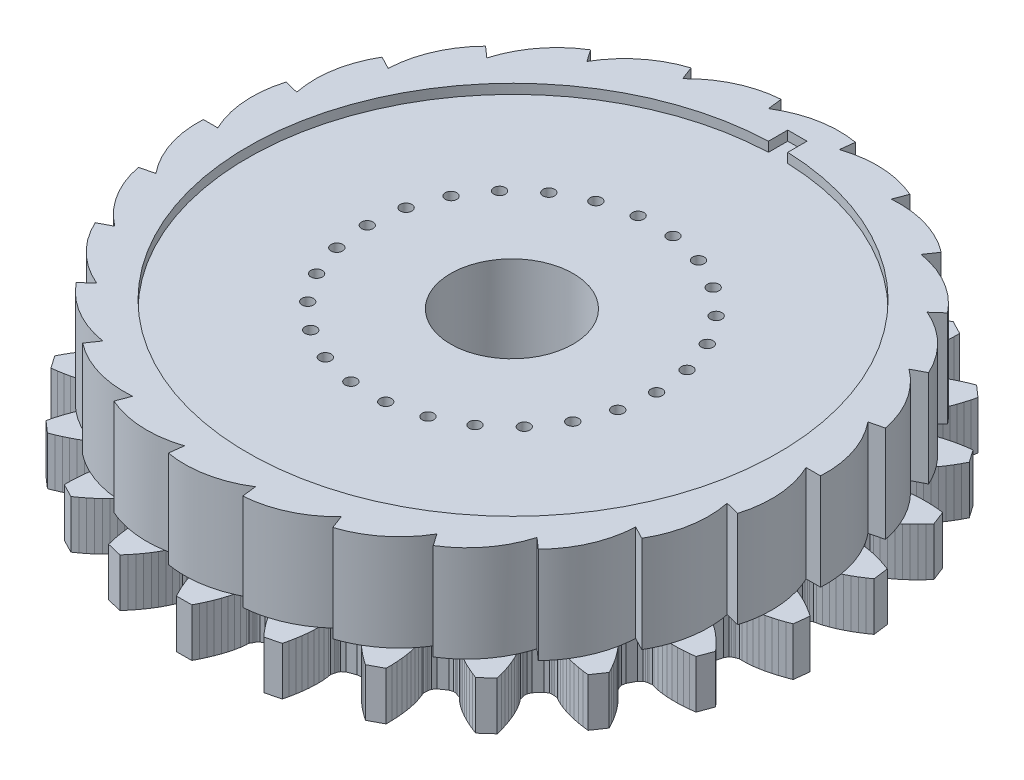
SolidWorks part; units mm, degrees
material "1060 Alloy"
ref_plane "Front Plane" through (0, 0, 0) normal (0, 0, 1) x (1, 0, 0)
ref_plane "Top Plane" through (0, 0, 0) normal (0, 1, 0) x (1, 0, 0)
ref_plane "Right Plane" through (0, 0, 0) normal (1, 0, 0) x (0, 0, -1)
sketch "Sketch1" plane through (0, 0, 0) normal (0, 1, 0) x (1, 0, 0)
  line L0 (0, 0) -> (54.8903, 0) construction
  line L1 (0, 0) -> (47.5263, 11.7142) construction
  line L2 (0, 0) -> (29.6137, 7.2991)
  line L3 (0, 0) -> (32, 0)
  circle A0 centre (0, 0) radius 32 construction
  circle A1 centre (0, 0) radius 30.5 construction
  arc A2 (29.6137, 7.2991) -> (32, 0) centre (21.3514, 0.5583) cw
  circle A3 centre (0, 0) radius 31.25 construction
  dimension "D1" = 62.5
  dimension "D2" = 1.5
  dimension "D4" = 0.75
  dimension "D3" = 13.846
extrude "Extrude ratchet edge" add sketch "Sketch1" along normal blind 10
pattern_circular "Pattern edge to form gear" count 26 over 360 about axis through (0, 10, 0) along (0, -1, 0) of "Extrude ratchet edge" reverse direction yes
sketch "Sketch7" plane through (0, 10, 0) normal (0, 1, 0) x (1, 0, 0)
  circle A0 centre (0, 0) radius 6.35
  dimension "D1" = 12.7
sketch "Sketch12" plane through (0, 0, 0) normal (0, -1, 0) x (1, 0, 0)
  line L0 (29.0003, -0.6166) -> (29.1196, -1.0003)
  line L1 (29.1196, -1.0003) -> (29.244, -1.1506)
  line L2 (29.244, -1.1506) -> (29.3694, -1.2597)
  line L3 (29.3694, -1.2597) -> (29.4955, -1.346)
  line L4 (29.4955, -1.346) -> (29.7463, -1.5351)
  line L5 (29.7463, -1.5351) -> (30.0039, -1.5796)
  line L6 (30.0039, -1.5796) -> (30.5166, -1.7122)
  line L7 (30.5166, -1.7122) -> (31.0266, -1.8861)
  line L8 (31.0266, -1.8861) -> (31.5336, -2.0936)
  line L9 (31.5336, -2.0936) -> (32.0376, -2.3308)
  line L10 (32.0376, -2.3308) -> (32.5381, -2.595)
  line L11 (32.5381, -2.595) -> (33.035, -2.8848)
  line L12 (33.035, -2.8848) -> (33.5277, -3.1987)
  line L13 (33.5277, -3.1987) -> (34.0159, -3.5359)
  line L14 (34.0159, -3.5359) -> (33.8164, -5.1042)
  line L15 (33.8164, -5.1042) -> (33.2594, -5.3084)
  line L16 (33.2594, -5.3084) -> (32.7038, -5.4891)
  line L17 (32.7038, -5.4891) -> (32.1503, -5.6453)
  line L18 (32.1503, -5.6453) -> (31.5995, -5.7759)
  line L19 (31.5995, -5.7759) -> (31.0523, -5.8793)
  line L20 (31.0523, -5.8793) -> (30.5094, -5.9534)
  line L21 (30.5094, -5.9534) -> (29.9722, -5.9942)
  line L22 (29.9722, -5.9942) -> (29.4426, -5.9942)
  line L23 (29.4426, -5.9942) -> (29.182, -5.9728)
  line L24 (29.182, -5.9728) -> (28.8919, -6.0931)
  line L25 (28.8919, -6.0931) -> (28.7482, -6.1452)
  line L26 (28.7482, -6.1452) -> (28.5995, -6.2194)
  line L27 (28.5995, -6.2194) -> (28.4414, -6.3338)
  line L28 (28.4414, -6.3338) -> (28.2299, -6.6755)
  line L29 (28.2299, -6.6755) -> (28.0119, -7.539)
  line L30 (28.0119, -7.539) -> (28.0359, -7.9401)
  line L31 (28.0359, -7.9401) -> (28.1207, -8.1159)
  line L32 (28.1207, -8.1159) -> (28.2164, -8.2517)
  line L33 (28.2164, -8.2517) -> (28.3182, -8.3658)
  line L34 (28.3182, -8.3658) -> (28.5164, -8.6094)
  line L35 (28.5164, -8.6094) -> (28.7559, -8.7142)
  line L36 (28.7559, -8.7142) -> (29.222, -8.9657)
  line L37 (29.222, -8.9657) -> (29.6755, -9.2566)
  line L38 (29.6755, -9.2566) -> (30.1181, -9.5794)
  line L39 (30.1181, -9.5794) -> (30.5507, -9.9303)
  line L40 (30.5507, -9.9303) -> (30.9735, -10.3067)
  line L41 (30.9735, -10.3067) -> (31.3865, -10.7069)
  line L42 (31.3865, -10.7069) -> (31.7898, -11.1296)
  line L43 (31.7898, -11.1296) -> (32.1831, -11.5738)
  line L44 (32.1831, -11.5738) -> (31.6141, -13.0488)
  line L45 (31.6141, -13.0488) -> (31.0244, -13.1138)
  line L46 (31.0244, -13.1138) -> (30.4418, -13.1563)
  line L47 (30.4418, -13.1563) -> (29.8669, -13.1754)
  line L48 (29.8669, -13.1754) -> (29.3009, -13.1704)
  line L49 (29.3009, -13.1704) -> (28.7448, -13.1399)
  line L50 (28.7448, -13.1399) -> (28.2, -13.0819)
  line L51 (28.2, -13.0819) -> (27.6686, -12.9929)
  line L52 (27.6686, -12.9929) -> (27.1544, -12.8663)
  line L53 (27.1544, -12.8663) -> (26.9065, -12.7831)
  line L54 (26.9065, -12.7831) -> (26.5961, -12.8305)
  line L55 (26.5961, -12.8305) -> (26.4441, -12.8467)
  line L56 (26.4441, -12.8467) -> (26.2819, -12.8831)
  line L57 (26.2819, -12.8831) -> (26.1011, -12.9564)
  line L58 (26.1011, -12.9564) -> (25.814, -13.2375)
  line L59 (25.814, -13.2375) -> (25.3956, -14.0238)
  line L60 (25.3956, -14.0238) -> (25.3229, -14.4189)
  line L61 (25.3229, -14.4189) -> (25.3632, -14.6099)
  line L62 (25.3632, -14.6099) -> (25.4236, -14.7647)
  line L63 (25.4236, -14.7647) -> (25.4951, -14.8998)
  line L64 (25.4951, -14.8998) -> (25.6292, -15.1838)
  line L65 (25.6292, -15.1838) -> (25.8367, -15.3428)
  line L66 (25.8367, -15.3428) -> (26.2291, -15.6985)
  line L67 (26.2291, -15.6985) -> (26.5998, -16.0895)
  line L68 (26.5998, -16.0895) -> (26.9523, -16.5089)
  line L69 (26.9523, -16.5089) -> (27.2883, -16.9531)
  line L70 (27.2883, -16.9531) -> (27.6087, -17.4197)
  line L71 (27.6087, -17.4197) -> (27.914, -17.9072)
  line L72 (27.914, -17.9072) -> (28.2044, -18.4141)
  line L73 (28.2044, -18.4141) -> (28.48, -18.9395)
  line L74 (28.48, -18.9395) -> (27.5746, -20.2355)
  line L75 (27.5746, -20.2355) -> (26.9864, -20.1575)
  line L76 (26.9864, -20.1575) -> (26.4105, -20.0593)
  line L77 (26.4105, -20.0593) -> (25.8478, -19.9403)
  line L78 (25.8478, -19.9403) -> (25.2994, -19.8)
  line L79 (25.2994, -19.8) -> (24.7668, -19.6373)
  line L80 (24.7668, -19.6373) -> (24.2517, -19.4506)
  line L81 (24.2517, -19.4506) -> (23.7571, -19.237)
  line L82 (23.7571, -19.237) -> (23.2881, -18.991)
  line L83 (23.2881, -18.991) -> (23.0673, -18.8509)
  line L84 (23.0673, -18.8509) -> (22.7546, -18.8226)
  line L85 (22.7546, -18.8226) -> (22.6031, -18.802)
  line L86 (22.6031, -18.802) -> (22.4369, -18.7985)
  line L87 (22.4369, -18.7985) -> (22.2438, -18.8264)
  line L88 (22.2438, -18.8264) -> (21.8978, -19.0306)
  line L89 (21.8978, -19.0306) -> (21.3034, -19.694)
  line L90 (21.3034, -19.694) -> (21.1383, -20.0602)
  line L91 (21.1383, -20.0602) -> (21.1316, -20.2553)
  line L92 (21.1316, -20.2553) -> (21.1532, -20.4201)
  line L93 (21.1532, -20.4201) -> (21.1903, -20.5684)
  line L94 (21.1903, -20.5684) -> (21.2526, -20.8761)
  line L95 (21.2526, -20.8761) -> (21.416, -21.0803)
  line L96 (21.416, -21.0803) -> (21.7119, -21.5195)
  line L97 (21.7119, -21.5195) -> (21.9782, -21.9879)
  line L98 (21.9782, -21.9879) -> (22.2201, -22.4794)
  line L99 (22.2201, -22.4794) -> (22.4401, -22.9911)
  line L100 (22.4401, -22.9911) -> (22.6395, -23.5209)
  line L101 (22.6395, -23.5209) -> (22.8193, -24.0672)
  line L102 (22.8193, -24.0672) -> (22.9799, -24.6289)
  line L103 (22.9799, -24.6289) -> (23.1217, -25.205)
  line L104 (23.1217, -25.205) -> (21.9325, -26.2467)
  line L105 (21.9325, -26.2467) -> (21.3801, -26.0302)
  line L106 (21.3801, -26.0302) -> (20.8445, -25.797)
  line L107 (20.8445, -25.797) -> (20.3266, -25.5468)
  line L108 (20.3266, -25.5468) -> (19.8277, -25.2793)
  line L109 (19.8277, -25.2793) -> (19.3494, -24.9939)
  line L110 (19.3494, -24.9939) -> (18.894, -24.6893)
  line L111 (18.894, -24.6893) -> (18.4649, -24.3636)
  line L112 (18.4649, -24.3636) -> (18.0684, -24.0125)
  line L113 (18.0684, -24.0125) -> (17.8876, -23.8237)
  line L114 (17.8876, -23.8237) -> (17.5907, -23.7213)
  line L115 (17.5907, -23.7213) -> (17.4485, -23.665)
  line L116 (17.4485, -23.665) -> (17.288, -23.6219)
  line L117 (17.288, -23.6219) -> (17.0938, -23.6028)
  line L118 (17.0938, -23.6028) -> (16.709, -23.7182)
  line L119 (16.709, -23.7182) -> (15.9732, -24.22)
  line L120 (15.9732, -24.22) -> (15.7251, -24.5362)
  line L121 (15.7251, -24.5362) -> (15.672, -24.7239)
  line L122 (15.672, -24.7239) -> (15.6536, -24.8891)
  line L123 (15.6536, -24.8891) -> (15.6541, -25.042)
  line L124 (15.6541, -25.042) -> (15.641, -25.3558)
  line L125 (15.641, -25.3558) -> (15.7507, -25.593)
  line L126 (15.7507, -25.593) -> (15.9329, -26.0903)
  line L127 (15.9329, -26.0903) -> (16.0794, -26.6088)
  line L128 (16.0794, -26.6088) -> (16.1966, -27.144)
  line L129 (16.1966, -27.144) -> (16.2878, -27.6934)
  line L130 (16.2878, -27.6934) -> (16.3546, -28.2555)
  line L131 (16.3546, -28.2555) -> (16.3984, -28.829)
  line L132 (16.3984, -28.829) -> (16.4199, -29.4128)
  line L133 (16.4199, -29.4128) -> (16.4198, -30.0061)
  line L134 (16.4198, -30.0061) -> (15.0158, -30.7329)
  line L135 (15.0158, -30.7329) -> (14.5313, -30.3905)
  line L136 (14.5313, -30.3905) -> (14.067, -30.0359)
  line L137 (14.067, -30.0359) -> (13.624, -29.6691)
  line L138 (13.624, -29.6691) -> (13.2037, -29.29)
  line L139 (13.2037, -29.29) -> (12.8076, -28.8984)
  line L140 (12.8076, -28.8984) -> (12.4383, -28.4937)
  line L141 (12.4383, -28.4937) -> (12.0996, -28.0747)
  line L142 (12.0996, -28.0747) -> (11.7986, -27.6389)
  line L143 (11.7986, -27.6389) -> (11.6683, -27.4123)
  line L144 (11.6683, -27.4123) -> (11.4045, -27.2419)
  line L145 (11.4045, -27.2419) -> (11.28, -27.1532)
  line L146 (11.28, -27.1532) -> (11.1345, -27.0729)
  line L147 (11.1345, -27.0729) -> (10.9505, -27.0079)
  line L148 (10.9505, -27.0079) -> (10.5492, -27.0279)
  line L149 (10.5492, -27.0279) -> (9.7146, -27.339)
  line L150 (9.7146, -27.339) -> (9.3982, -27.5866)
  line L151 (9.3982, -27.5866) -> (9.3017, -27.7562)
  line L152 (9.3017, -27.7562) -> (9.2442, -27.9122)
  line L153 (9.2442, -27.9122) -> (9.2082, -28.0607)
  line L154 (9.2082, -28.0607) -> (9.1203, -28.3622)
  line L155 (9.1203, -28.3622) -> (9.1701, -28.6189)
  line L156 (9.1701, -28.6189) -> (9.2279, -29.1453)
  line L157 (9.2279, -29.1453) -> (9.2461, -29.6838)
  line L158 (9.2461, -29.6838) -> (9.2319, -30.2315)
  line L159 (9.2319, -30.2315) -> (9.1888, -30.7868)
  line L160 (9.1888, -30.7868) -> (9.1192, -31.3485)
  line L161 (9.1192, -31.3485) -> (9.0245, -31.9158)
  line L162 (9.0245, -31.9158) -> (8.9057, -32.4878)
  line L163 (8.9057, -32.4878) -> (8.7636, -33.0638)
  line L164 (8.7636, -33.0638) -> (7.2264, -33.4335)
  line L165 (7.2264, -33.4335) -> (6.8379, -32.9851)
  line L166 (6.8379, -32.9851) -> (6.472, -32.5297)
  line L167 (6.472, -32.5297) -> (6.1297, -32.0675)
  line L168 (6.1297, -32.0675) -> (5.8123, -31.5988)
  line L169 (5.8123, -31.5988) -> (5.5215, -31.1238)
  line L170 (5.5215, -31.1238) -> (5.2598, -30.6425)
  line L171 (5.2598, -30.6425) -> (5.0311, -30.1547)
  line L172 (5.0311, -30.1547) -> (4.8432, -29.6595)
  line L173 (4.8432, -29.6595) -> (4.7709, -29.4083)
  line L174 (4.7709, -29.4083) -> (4.5555, -29.1797)
  line L175 (4.5555, -29.1797) -> (4.4559, -29.0638)
  line L176 (4.4559, -29.0638) -> (4.3338, -28.951)
  line L177 (4.3338, -28.951) -> (4.1707, -28.8438)
  line L178 (4.1707, -28.8438) -> (3.7763, -28.7672)
  line L179 (3.7763, -28.7672) -> (2.8915, -28.8696)
  line L180 (2.8915, -28.8696) -> (2.525, -29.0342)
  line L181 (2.525, -29.0342) -> (2.3907, -29.1758)
  line L182 (2.3907, -29.1758) -> (2.2976, -29.3135)
  line L183 (2.2976, -29.3135) -> (2.2271, -29.4491)
  line L184 (2.2271, -29.4491) -> (2.0696, -29.7208)
  line L185 (2.0696, -29.7208) -> (2.0565, -29.9819)
  line L186 (2.0565, -29.9819) -> (1.9867, -30.5069)
  line L187 (1.9867, -30.5069) -> (1.8755, -31.0341)
  line L188 (1.8755, -31.0341) -> (1.7306, -31.5624)
  line L189 (1.7306, -31.5624) -> (1.5559, -32.0913)
  line L190 (1.5559, -32.0913) -> (1.3539, -32.6201)
  line L191 (1.3539, -32.6201) -> (1.1262, -33.1482)
  line L192 (1.1262, -33.1482) -> (0.8739, -33.6752)
  line L193 (0.8739, -33.6752) -> (0.5981, -34.2004)
  line L194 (0.5981, -34.2004) -> (-0.9829, -34.1915)
  line L195 (-0.9829, -34.1915) -> (-1.2528, -33.6632)
  line L196 (-1.2528, -33.6632) -> (-1.499, -33.1334)
  line L197 (-1.499, -33.1334) -> (-1.7208, -32.6027)
  line L198 (-1.7208, -32.6027) -> (-1.9169, -32.0717)
  line L199 (-1.9169, -32.0717) -> (-2.0855, -31.5409)
  line L200 (-2.0855, -31.5409) -> (-2.2244, -31.011)
  line L201 (-2.2244, -31.011) -> (-2.3297, -30.4826)
  line L202 (-2.3297, -30.4826) -> (-2.3936, -29.9568)
  line L203 (-2.3936, -29.9568) -> (-2.4037, -29.6956)
  line L204 (-2.4037, -29.6956) -> (-2.5581, -29.4221)
  line L205 (-2.5581, -29.4221) -> (-2.6272, -29.2857)
  line L206 (-2.6272, -29.2857) -> (-2.7187, -29.147)
  line L207 (-2.7187, -29.147) -> (-2.8514, -29.0039)
  line L208 (-2.8514, -29.0039) -> (-3.216, -28.8351)
  line L209 (-3.216, -28.8351) -> (-4.0996, -28.7228)
  line L210 (-4.0996, -28.7228) -> (-4.4948, -28.7949)
  line L211 (-4.4948, -28.7949) -> (-4.6591, -28.9003)
  line L212 (-4.6591, -28.9003) -> (-4.7824, -29.0117)
  line L213 (-4.7824, -29.0117) -> (-4.8834, -29.1265)
  line L214 (-4.8834, -29.1265) -> (-5.1013, -29.3526)
  line L215 (-5.1013, -29.3526) -> (-5.1765, -29.603)
  line L216 (-5.1765, -29.603) -> (-5.37, -30.096)
  line L217 (-5.37, -30.096) -> (-5.6041, -30.5812)
  line L218 (-5.6041, -30.5812) -> (-5.8712, -31.0596)
  line L219 (-5.8712, -31.0596) -> (-6.1674, -31.5313)
  line L220 (-6.1674, -31.5313) -> (-6.4901, -31.9963)
  line L221 (-6.4901, -31.9963) -> (-6.8376, -32.4546)
  line L222 (-6.8376, -32.4546) -> (-7.2086, -32.9059)
  line L223 (-7.2086, -32.9059) -> (-7.6021, -33.3499)
  line L224 (-7.6021, -33.3499) -> (-9.135, -32.9629)
  line L225 (-9.135, -32.9629) -> (-9.2706, -32.3853)
  line L226 (-9.2706, -32.3853) -> (-9.383, -31.812)
  line L227 (-9.383, -31.812) -> (-9.4713, -31.2437)
  line L228 (-9.4713, -31.2437) -> (-9.5346, -30.6812)
  line L229 (-9.5346, -30.6812) -> (-9.5713, -30.1254)
  line L230 (-9.5713, -30.1254) -> (-9.5793, -29.5776)
  line L231 (-9.5793, -29.5776) -> (-9.5551, -29.0394)
  line L232 (-9.5551, -29.0394) -> (-9.4913, -28.5136)
  line L233 (-9.4913, -28.5136) -> (-9.4387, -28.2576)
  line L234 (-9.4387, -28.2576) -> (-9.5231, -27.9551)
  line L235 (-9.5231, -27.9551) -> (-9.5575, -27.8061)
  line L236 (-9.5575, -27.8061) -> (-9.6132, -27.6496)
  line L237 (-9.6132, -27.6496) -> (-9.7078, -27.4789)
  line L238 (-9.7078, -27.4789) -> (-10.0214, -27.2277)
  line L239 (-10.0214, -27.2277) -> (-10.8524, -26.9072)
  line L240 (-10.8524, -26.9072) -> (-11.2535, -26.8827)
  line L241 (-11.2535, -26.8827) -> (-11.4382, -26.9456)
  line L242 (-11.4382, -26.9456) -> (-11.5846, -27.0243)
  line L243 (-11.5846, -27.0243) -> (-11.7101, -27.1116)
  line L244 (-11.7101, -27.1116) -> (-11.9758, -27.279)
  line L245 (-11.9758, -27.279) -> (-12.1087, -27.5041)
  line L246 (-12.1087, -27.5041) -> (-12.4145, -27.9365)
  line L247 (-12.4145, -27.9365) -> (-12.758, -28.3516)
  line L248 (-12.758, -28.3516) -> (-13.1318, -28.7521)
  line L249 (-13.1318, -28.7521) -> (-13.5322, -29.1392)
  line L250 (-13.5322, -29.1392) -> (-13.9568, -29.5135)
  line L251 (-13.9568, -29.5135) -> (-14.4039, -29.8753)
  line L252 (-14.4039, -29.8753) -> (-14.8722, -30.2247)
  line L253 (-14.8722, -30.2247) -> (-15.3605, -30.5616)
  line L254 (-15.3605, -30.5616) -> (-16.7562, -29.819)
  line L255 (-16.7562, -29.819) -> (-16.7497, -29.2258)
  line L256 (-16.7497, -29.2258) -> (-16.7216, -28.6422)
  line L257 (-16.7216, -28.6422) -> (-16.6713, -28.0693)
  line L258 (-16.6713, -28.0693) -> (-16.5981, -27.508)
  line L259 (-16.5981, -27.508) -> (-16.5008, -26.9596)
  line L260 (-16.5008, -26.9596) -> (-16.3775, -26.4258)
  line L261 (-16.3775, -26.4258) -> (-16.2252, -25.909)
  line L262 (-16.2252, -25.909) -> (-16.0374, -25.4138)
  line L263 (-16.0374, -25.4138) -> (-15.925, -25.1778)
  line L264 (-15.925, -25.1778) -> (-15.9346, -24.8639)
  line L265 (-15.9346, -24.8639) -> (-15.9324, -24.711)
  line L266 (-15.9324, -24.711) -> (-15.949, -24.5456)
  line L267 (-15.949, -24.5456) -> (-15.9999, -24.3573)
  line L268 (-15.9999, -24.3573) -> (-16.2444, -24.0384)
  line L269 (-16.2444, -24.0384) -> (-16.9745, -23.5283)
  line L270 (-16.9745, -23.5283) -> (-17.358, -23.4085)
  line L271 (-17.358, -23.4085) -> (-17.5524, -23.4254)
  line L272 (-17.5524, -23.4254) -> (-17.7134, -23.4668)
  line L273 (-17.7134, -23.4668) -> (-17.8562, -23.5215)
  line L274 (-17.8562, -23.5215) -> (-18.1542, -23.6204)
  line L275 (-18.1542, -23.6204) -> (-18.3371, -23.8072)
  line L276 (-18.3371, -23.8072) -> (-18.7375, -24.1538)
  line L277 (-18.7375, -24.1538) -> (-19.1704, -24.4747)
  line L278 (-19.1704, -24.4747) -> (-19.6292, -24.7741)
  line L279 (-19.6292, -24.7741) -> (-20.1106, -25.0541)
  line L280 (-20.1106, -25.0541) -> (-20.6125, -25.316)
  line L281 (-20.6125, -25.316) -> (-21.1332, -25.5603)
  line L282 (-21.1332, -25.5603) -> (-21.6714, -25.7874)
  line L283 (-21.6714, -25.7874) -> (-22.2262, -25.9977)
  line L284 (-22.2262, -25.9977) -> (-23.4036, -24.9426)
  line L285 (-23.4036, -24.9426) -> (-23.2553, -24.3682)
  line L286 (-23.2553, -24.3682) -> (-23.0883, -23.8083)
  line L287 (-23.0883, -23.8083) -> (-22.9024, -23.2641)
  line L288 (-22.9024, -23.2641) -> (-22.6971, -22.7366)
  line L289 (-22.6971, -22.7366) -> (-22.4713, -22.2274)
  line L290 (-22.4713, -22.2274) -> (-22.2239, -21.7386)
  line L291 (-22.2239, -21.7386) -> (-21.9523, -21.2733)
  line L292 (-21.9523, -21.2733) -> (-21.6515, -20.8374)
  line L293 (-21.6515, -20.8374) -> (-21.4858, -20.6352)
  line L294 (-21.4858, -20.6352) -> (-21.4201, -20.3281)
  line L295 (-21.4201, -20.3281) -> (-21.3813, -20.1802)
  line L296 (-21.3813, -20.1802) -> (-21.3578, -20.0157)
  line L297 (-21.3578, -20.0157) -> (-21.3622, -19.8206)
  line L298 (-21.3622, -19.8206) -> (-21.5232, -19.4525)
  line L299 (-21.5232, -19.4525) -> (-22.1101, -18.7825)
  line L300 (-22.1101, -18.7825) -> (-22.4538, -18.5744)
  line L301 (-22.4538, -18.5744) -> (-22.6466, -18.5443)
  line L302 (-22.6466, -18.5443) -> (-22.8128, -18.5459)
  line L303 (-22.8128, -18.5459) -> (-22.9645, -18.5648)
  line L304 (-22.9645, -18.5648) -> (-23.2775, -18.5896)
  line L305 (-23.2775, -18.5896) -> (-23.4999, -18.7272)
  line L306 (-23.4999, -18.7272) -> (-23.9716, -18.9679)
  line L307 (-23.9716, -18.9679) -> (-24.4686, -19.1758)
  line L308 (-24.4686, -19.1758) -> (-24.9858, -19.3568)
  line L309 (-24.9858, -19.3568) -> (-25.5202, -19.5135)
  line L310 (-25.5202, -19.5135) -> (-26.0702, -19.6476)
  line L311 (-26.0702, -19.6476) -> (-26.6342, -19.7602)
  line L312 (-26.6342, -19.7602) -> (-27.2111, -19.8519)
  line L313 (-27.2111, -19.8519) -> (-27.8001, -19.9233)
  line L314 (-27.8001, -19.9233) -> (-28.6909, -18.6171)
  line L315 (-28.6909, -18.6171) -> (-28.4094, -18.0949)
  line L316 (-28.4094, -18.0949) -> (-28.1133, -17.5912)
  line L317 (-28.1133, -17.5912) -> (-27.8025, -17.1073)
  line L318 (-27.8025, -17.1073) -> (-27.4769, -16.6443)
  line L319 (-27.4769, -16.6443) -> (-27.1359, -16.2039)
  line L320 (-27.1359, -16.2039) -> (-26.7786, -15.7885)
  line L321 (-26.7786, -15.7885) -> (-26.4036, -15.4018)
  line L322 (-26.4036, -15.4018) -> (-26.0072, -15.0505)
  line L323 (-26.0072, -15.0505) -> (-25.7979, -14.8938)
  line L324 (-25.7979, -14.8938) -> (-25.6606, -14.6114)
  line L325 (-25.6606, -14.6114) -> (-25.5876, -14.4771)
  line L326 (-25.5876, -14.4771) -> (-25.5254, -14.3229)
  line L327 (-25.5254, -14.3229) -> (-25.483, -14.1325)
  line L328 (-25.483, -14.1325) -> (-25.5512, -13.7365)
  line L329 (-25.5512, -13.7365) -> (-25.9607, -12.9455)
  line L330 (-25.9607, -12.9455) -> (-26.2446, -12.6612)
  line L331 (-26.2446, -12.6612) -> (-26.4246, -12.5859)
  line L332 (-26.4246, -12.5859) -> (-26.5864, -12.5476)
  line L333 (-26.5864, -12.5476) -> (-26.7382, -12.5297)
  line L334 (-26.7382, -12.5297) -> (-27.0481, -12.4789)
  line L335 (-27.0481, -12.4789) -> (-27.2968, -12.5592)
  line L336 (-27.2968, -12.5592) -> (-27.8125, -12.6801)
  line L337 (-27.8125, -12.6801) -> (-28.3448, -12.763)
  line L338 (-28.3448, -12.763) -> (-28.8902, -12.8149)
  line L339 (-28.8902, -12.8149) -> (-29.4467, -12.8392)
  line L340 (-29.4467, -12.8392) -> (-30.0127, -12.8378)
  line L341 (-30.0127, -12.8378) -> (-30.5873, -12.8121)
  line L342 (-30.5873, -12.8121) -> (-31.1694, -12.7631)
  line L343 (-31.1694, -12.7631) -> (-31.7584, -12.6915)
  line L344 (-31.7584, -12.6915) -> (-32.3107, -11.2101)
  line L345 (-32.3107, -11.2101) -> (-31.9124, -10.7704)
  line L346 (-31.9124, -10.7704) -> (-31.5044, -10.3522)
  line L347 (-31.5044, -10.3522) -> (-31.0868, -9.9567)
  line L348 (-31.0868, -9.9567) -> (-30.6598, -9.5851)
  line L349 (-30.6598, -9.5851) -> (-30.2233, -9.2392)
  line L350 (-30.2233, -9.2392) -> (-29.7771, -8.9214)
  line L351 (-29.7771, -8.9214) -> (-29.3203, -8.6356)
  line L352 (-29.3203, -8.6356) -> (-28.8514, -8.3894)
  line L353 (-28.8514, -8.3894) -> (-28.6108, -8.2873)
  line L354 (-28.6108, -8.2873) -> (-28.4098, -8.0459)
  line L355 (-28.4098, -8.0459) -> (-28.3068, -7.933)
  line L356 (-28.3068, -7.933) -> (-28.2095, -7.7982)
  line L357 (-28.2095, -7.7982) -> (-28.1228, -7.6234)
  line L358 (-28.1228, -7.6234) -> (-28.0943, -7.2226)
  line L359 (-28.0943, -7.2226) -> (-28.3025, -6.3567)
  line L360 (-28.3025, -6.3567) -> (-28.5102, -6.0127)
  line L361 (-28.5102, -6.0127) -> (-28.6669, -5.8964)
  line L362 (-28.6669, -5.8964) -> (-28.8148, -5.8206)
  line L363 (-28.8148, -5.8206) -> (-28.9579, -5.7669)
  line L364 (-28.9579, -5.7669) -> (-29.2466, -5.6433)
  line L365 (-29.2466, -5.6433) -> (-29.5074, -5.6618)
  line L366 (-29.5074, -5.6618) -> (-30.037, -5.6558)
  line L367 (-30.037, -5.6558) -> (-30.5737, -5.6089)
  line L368 (-30.5737, -5.6089) -> (-31.1157, -5.5288)
  line L369 (-31.1157, -5.5288) -> (-31.6618, -5.4192)
  line L370 (-31.6618, -5.4192) -> (-32.211, -5.2824)
  line L371 (-32.211, -5.2824) -> (-32.7628, -5.1199)
  line L372 (-32.7628, -5.1199) -> (-33.3163, -4.933)
  line L373 (-33.3163, -4.933) -> (-33.871, -4.7225)
  line L374 (-33.871, -4.7225) -> (-34.0527, -3.152)
  line L375 (-34.0527, -3.152) -> (-33.5607, -2.8204)
  line L376 (-33.5607, -2.8204) -> (-33.0645, -2.5121)
  line L377 (-33.0645, -2.5121) -> (-32.5644, -2.228)
  line L378 (-32.5644, -2.228) -> (-32.0609, -1.9693)
  line L379 (-32.0609, -1.9693) -> (-31.5543, -1.7379)
  line L380 (-31.5543, -1.7379) -> (-31.045, -1.5361)
  line L381 (-31.045, -1.5361) -> (-30.5331, -1.3679)
  line L382 (-30.5331, -1.3679) -> (-30.0189, -1.2411)
  line L383 (-30.0189, -1.2411) -> (-29.7608, -1.1996)
  line L384 (-29.7608, -1.1996) -> (-29.5079, -1.0133)
  line L385 (-29.5079, -1.0133) -> (-29.3809, -0.9284)
  line L386 (-29.3809, -0.9284) -> (-29.2542, -0.8208)
  line L387 (-29.2542, -0.8208) -> (-29.1281, -0.6718)
  line L388 (-29.1281, -0.6718) -> (-29.0045, -0.2895)
  line L389 (-29.0045, -0.2895) -> (-28.9995, 0.6011)
  line L390 (-28.9995, 0.6011) -> (-29.1188, 0.9848)
  line L391 (-29.1188, 0.9848) -> (-29.2432, 1.1352)
  line L392 (-29.2432, 1.1352) -> (-29.3686, 1.2442)
  line L393 (-29.3686, 1.2442) -> (-29.4947, 1.3306)
  line L394 (-29.4947, 1.3306) -> (-29.7455, 1.5197)
  line L395 (-29.7455, 1.5197) -> (-30.0031, 1.5641)
  line L396 (-30.0031, 1.5641) -> (-30.5158, 1.6968)
  line L397 (-30.5158, 1.6968) -> (-31.0257, 1.8707)
  line L398 (-31.0257, 1.8707) -> (-31.5328, 2.0782)
  line L399 (-31.5328, 2.0782) -> (-32.0368, 2.3153)
  line L400 (-32.0368, 2.3153) -> (-32.5373, 2.5796)
  line L401 (-32.5373, 2.5796) -> (-33.0342, 2.8694)
  line L402 (-33.0342, 2.8694) -> (-33.5269, 3.1833)
  line L403 (-33.5269, 3.1833) -> (-34.0151, 3.5204)
  line L404 (-34.0151, 3.5204) -> (-33.8156, 5.0888)
  line L405 (-33.8156, 5.0888) -> (-33.2586, 5.293)
  line L406 (-33.2586, 5.293) -> (-32.703, 5.4737)
  line L407 (-32.703, 5.4737) -> (-32.1495, 5.6298)
  line L408 (-32.1495, 5.6298) -> (-31.5987, 5.7604)
  line L409 (-31.5987, 5.7604) -> (-31.0515, 5.8639)
  line L410 (-31.0515, 5.8639) -> (-30.5086, 5.9379)
  line L411 (-30.5086, 5.9379) -> (-29.9714, 5.9787)
  line L412 (-29.9714, 5.9787) -> (-29.4418, 5.9788)
  line L413 (-29.4418, 5.9788) -> (-29.1812, 5.9574)
  line L414 (-29.1812, 5.9574) -> (-28.8911, 6.0777)
  line L415 (-28.8911, 6.0777) -> (-28.7474, 6.1298)
  line L416 (-28.7474, 6.1298) -> (-28.5987, 6.2039)
  line L417 (-28.5987, 6.2039) -> (-28.4406, 6.3184)
  line L418 (-28.4406, 6.3184) -> (-28.2291, 6.66)
  line L419 (-28.2291, 6.66) -> (-28.0111, 7.5236)
  line L420 (-28.0111, 7.5236) -> (-28.0351, 7.9247)
  line L421 (-28.0351, 7.9247) -> (-28.1199, 8.1004)
  line L422 (-28.1199, 8.1004) -> (-28.2156, 8.2363)
  line L423 (-28.2156, 8.2363) -> (-28.3174, 8.3504)
  line L424 (-28.3174, 8.3504) -> (-28.5156, 8.594)
  line L425 (-28.5156, 8.594) -> (-28.7551, 8.6988)
  line L426 (-28.7551, 8.6988) -> (-29.2212, 8.9502)
  line L427 (-29.2212, 8.9502) -> (-29.6746, 9.2412)
  line L428 (-29.6746, 9.2412) -> (-30.1173, 9.564)
  line L429 (-30.1173, 9.564) -> (-30.5499, 9.9148)
  line L430 (-30.5499, 9.9148) -> (-30.9727, 10.2912)
  line L431 (-30.9727, 10.2912) -> (-31.3857, 10.6914)
  line L432 (-31.3857, 10.6914) -> (-31.789, 11.1142)
  line L433 (-31.789, 11.1142) -> (-32.1823, 11.5583)
  line L434 (-32.1823, 11.5583) -> (-31.6133, 13.0334)
  line L435 (-31.6133, 13.0334) -> (-31.0236, 13.0984)
  line L436 (-31.0236, 13.0984) -> (-30.4409, 13.1408)
  line L437 (-30.4409, 13.1408) -> (-29.8661, 13.16)
  line L438 (-29.8661, 13.16) -> (-29.3001, 13.155)
  line L439 (-29.3001, 13.155) -> (-28.744, 13.1245)
  line L440 (-28.744, 13.1245) -> (-28.1992, 13.0665)
  line L441 (-28.1992, 13.0665) -> (-27.6678, 12.9775)
  line L442 (-27.6678, 12.9775) -> (-27.1536, 12.8508)
  line L443 (-27.1536, 12.8508) -> (-26.9057, 12.7677)
  line L444 (-26.9057, 12.7677) -> (-26.5953, 12.8151)
  line L445 (-26.5953, 12.8151) -> (-26.4433, 12.8312)
  line L446 (-26.4433, 12.8312) -> (-26.2811, 12.8676)
  line L447 (-26.2811, 12.8676) -> (-26.1002, 12.941)
  line L448 (-26.1002, 12.941) -> (-25.8131, 13.222)
  line L449 (-25.8131, 13.222) -> (-25.3948, 14.0083)
  line L450 (-25.3948, 14.0083) -> (-25.3221, 14.4035)
  line L451 (-25.3221, 14.4035) -> (-25.3623, 14.5945)
  line L452 (-25.3623, 14.5945) -> (-25.4228, 14.7493)
  line L453 (-25.4228, 14.7493) -> (-25.4943, 14.8844)
  line L454 (-25.4943, 14.8844) -> (-25.6284, 15.1683)
  line L455 (-25.6284, 15.1683) -> (-25.8359, 15.3274)
  line L456 (-25.8359, 15.3274) -> (-26.2283, 15.6831)
  line L457 (-26.2283, 15.6831) -> (-26.5989, 16.0741)
  line L458 (-26.5989, 16.0741) -> (-26.9515, 16.4935)
  line L459 (-26.9515, 16.4935) -> (-27.2875, 16.9377)
  line L460 (-27.2875, 16.9377) -> (-27.6079, 17.4043)
  line L461 (-27.6079, 17.4043) -> (-27.9132, 17.8917)
  line L462 (-27.9132, 17.8917) -> (-28.2036, 18.3987)
  line L463 (-28.2036, 18.3987) -> (-28.4792, 18.9241)
  line L464 (-28.4792, 18.9241) -> (-27.5738, 20.2201)
  line L465 (-27.5738, 20.2201) -> (-26.9856, 20.1421)
  line L466 (-26.9856, 20.1421) -> (-26.4097, 20.0438)
  line L467 (-26.4097, 20.0438) -> (-25.847, 19.9249)
  line L468 (-25.847, 19.9249) -> (-25.2986, 19.7846)
  line L469 (-25.2986, 19.7846) -> (-24.766, 19.6219)
  line L470 (-24.766, 19.6219) -> (-24.2509, 19.4351)
  line L471 (-24.2509, 19.4351) -> (-23.7562, 19.2216)
  line L472 (-23.7562, 19.2216) -> (-23.2873, 18.9756)
  line L473 (-23.2873, 18.9756) -> (-23.0665, 18.8355)
  line L474 (-23.0665, 18.8355) -> (-22.7538, 18.8072)
  line L475 (-22.7538, 18.8072) -> (-22.6023, 18.7865)
  line L476 (-22.6023, 18.7865) -> (-22.4361, 18.7831)
  line L477 (-22.4361, 18.7831) -> (-22.243, 18.811)
  line L478 (-22.243, 18.811) -> (-21.897, 19.0152)
  line L479 (-21.897, 19.0152) -> (-21.3026, 19.6785)
  line L480 (-21.3026, 19.6785) -> (-21.1374, 20.0448)
  line L481 (-21.1374, 20.0448) -> (-21.1308, 20.2399)
  line L482 (-21.1308, 20.2399) -> (-21.1524, 20.4046)
  line L483 (-21.1524, 20.4046) -> (-21.1895, 20.5529)
  line L484 (-21.1895, 20.5529) -> (-21.2518, 20.8607)
  line L485 (-21.2518, 20.8607) -> (-21.4152, 21.0648)
  line L486 (-21.4152, 21.0648) -> (-21.7111, 21.5041)
  line L487 (-21.7111, 21.5041) -> (-21.9774, 21.9724)
  line L488 (-21.9774, 21.9724) -> (-22.2193, 22.464)
  line L489 (-22.2193, 22.464) -> (-22.4393, 22.9757)
  line L490 (-22.4393, 22.9757) -> (-22.6387, 23.5054)
  line L491 (-22.6387, 23.5054) -> (-22.8185, 24.0518)
  line L492 (-22.8185, 24.0518) -> (-22.9791, 24.6135)
  line L493 (-22.9791, 24.6135) -> (-23.1209, 25.1896)
  line L494 (-23.1209, 25.1896) -> (-21.9317, 26.2312)
  line L495 (-21.9317, 26.2312) -> (-21.3793, 26.0148)
  line L496 (-21.3793, 26.0148) -> (-20.8436, 25.7815)
  line L497 (-20.8436, 25.7815) -> (-20.3258, 25.5314)
  line L498 (-20.3258, 25.5314) -> (-19.8269, 25.2639)
  line L499 (-19.8269, 25.2639) -> (-19.3486, 24.9785)
  line L500 (-19.3486, 24.9785) -> (-18.8932, 24.6739)
  line L501 (-18.8932, 24.6739) -> (-18.464, 24.3482)
  line L502 (-18.464, 24.3482) -> (-18.0676, 23.997)
  line L503 (-18.0676, 23.997) -> (-17.8868, 23.8082)
  line L504 (-17.8868, 23.8082) -> (-17.5899, 23.7059)
  line L505 (-17.5899, 23.7059) -> (-17.4477, 23.6496)
  line L506 (-17.4477, 23.6496) -> (-17.2872, 23.6065)
  line L507 (-17.2872, 23.6065) -> (-17.093, 23.5873)
  line L508 (-17.093, 23.5873) -> (-16.7082, 23.7028)
  line L509 (-16.7082, 23.7028) -> (-15.9723, 24.2046)
  line L510 (-15.9723, 24.2046) -> (-15.7243, 24.5207)
  line L511 (-15.7243, 24.5207) -> (-15.6712, 24.7085)
  line L512 (-15.6712, 24.7085) -> (-15.6528, 24.8737)
  line L513 (-15.6528, 24.8737) -> (-15.6533, 25.0266)
  line L514 (-15.6533, 25.0266) -> (-15.6401, 25.3403)
  line L515 (-15.6401, 25.3403) -> (-15.7499, 25.5776)
  line L516 (-15.7499, 25.5776) -> (-15.932, 26.0749)
  line L517 (-15.932, 26.0749) -> (-16.0786, 26.5934)
  line L518 (-16.0786, 26.5934) -> (-16.1958, 27.1285)
  line L519 (-16.1958, 27.1285) -> (-16.2869, 27.678)
  line L520 (-16.2869, 27.678) -> (-16.3538, 28.2401)
  line L521 (-16.3538, 28.2401) -> (-16.3976, 28.8136)
  line L522 (-16.3976, 28.8136) -> (-16.4191, 29.3974)
  line L523 (-16.4191, 29.3974) -> (-16.419, 29.9907)
  line L524 (-16.419, 29.9907) -> (-15.015, 30.7175)
  line L525 (-15.015, 30.7175) -> (-14.5305, 30.3751)
  line L526 (-14.5305, 30.3751) -> (-14.0662, 30.0205)
  line L527 (-14.0662, 30.0205) -> (-13.6232, 29.6536)
  line L528 (-13.6232, 29.6536) -> (-13.2028, 29.2746)
  line L529 (-13.2028, 29.2746) -> (-12.8068, 28.8829)
  line L530 (-12.8068, 28.8829) -> (-12.4375, 28.4782)
  line L531 (-12.4375, 28.4782) -> (-12.0988, 28.0593)
  line L532 (-12.0988, 28.0593) -> (-11.7978, 27.6235)
  line L533 (-11.7978, 27.6235) -> (-11.6675, 27.3969)
  line L534 (-11.6675, 27.3969) -> (-11.4037, 27.2265)
  line L535 (-11.4037, 27.2265) -> (-11.2792, 27.1378)
  line L536 (-11.2792, 27.1378) -> (-11.1336, 27.0575)
  line L537 (-11.1336, 27.0575) -> (-10.9497, 26.9924)
  line L538 (-10.9497, 26.9924) -> (-10.5484, 27.0125)
  line L539 (-10.5484, 27.0125) -> (-9.7138, 27.3236)
  line L540 (-9.7138, 27.3236) -> (-9.3974, 27.5712)
  line L541 (-9.3974, 27.5712) -> (-9.3009, 27.7408)
  line L542 (-9.3009, 27.7408) -> (-9.2434, 27.8967)
  line L543 (-9.2434, 27.8967) -> (-9.2073, 28.0453)
  line L544 (-9.2073, 28.0453) -> (-9.1195, 28.3468)
  line L545 (-9.1195, 28.3468) -> (-9.1693, 28.6034)
  line L546 (-9.1693, 28.6034) -> (-9.2271, 29.1299)
  line L547 (-9.2271, 29.1299) -> (-9.2453, 29.6683)
  line L548 (-9.2453, 29.6683) -> (-9.231, 30.216)
  line L549 (-9.231, 30.216) -> (-9.188, 30.7713)
  line L550 (-9.188, 30.7713) -> (-9.1184, 31.3331)
  line L551 (-9.1184, 31.3331) -> (-9.0237, 31.9004)
  line L552 (-9.0237, 31.9004) -> (-8.9049, 32.4724)
  line L553 (-8.9049, 32.4724) -> (-8.7628, 33.0484)
  line L554 (-8.7628, 33.0484) -> (-7.2256, 33.4181)
  line L555 (-7.2256, 33.4181) -> (-6.8371, 32.9697)
  line L556 (-6.8371, 32.9697) -> (-6.4712, 32.5142)
  line L557 (-6.4712, 32.5142) -> (-6.1289, 32.0521)
  line L558 (-6.1289, 32.0521) -> (-5.8115, 31.5834)
  line L559 (-5.8115, 31.5834) -> (-5.5207, 31.1084)
  line L560 (-5.5207, 31.1084) -> (-5.259, 30.6271)
  line L561 (-5.259, 30.6271) -> (-5.0303, 30.1392)
  line L562 (-5.0303, 30.1392) -> (-4.8424, 29.644)
  line L563 (-4.8424, 29.644) -> (-4.7701, 29.3928)
  line L564 (-4.7701, 29.3928) -> (-4.5547, 29.1643)
  line L565 (-4.5547, 29.1643) -> (-4.4551, 29.0483)
  line L566 (-4.4551, 29.0483) -> (-4.333, 28.9356)
  line L567 (-4.333, 28.9356) -> (-4.1699, 28.8284)
  line L568 (-4.1699, 28.8284) -> (-3.7755, 28.7518)
  line L569 (-3.7755, 28.7518) -> (-2.8907, 28.8541)
  line L570 (-2.8907, 28.8541) -> (-2.5242, 29.0188)
  line L571 (-2.5242, 29.0188) -> (-2.3899, 29.1604)
  line L572 (-2.3899, 29.1604) -> (-2.2968, 29.2981)
  line L573 (-2.2968, 29.2981) -> (-2.2263, 29.4337)
  line L574 (-2.2263, 29.4337) -> (-2.0688, 29.7054)
  line L575 (-2.0688, 29.7054) -> (-2.0557, 29.9665)
  line L576 (-2.0557, 29.9665) -> (-1.9859, 30.4915)
  line L577 (-1.9859, 30.4915) -> (-1.8747, 31.0186)
  line L578 (-1.8747, 31.0186) -> (-1.7298, 31.547)
  line L579 (-1.7298, 31.547) -> (-1.5551, 32.0759)
  line L580 (-1.5551, 32.0759) -> (-1.3531, 32.6047)
  line L581 (-1.3531, 32.6047) -> (-1.1254, 33.1328)
  line L582 (-1.1254, 33.1328) -> (-0.8731, 33.6597)
  line L583 (-0.8731, 33.6597) -> (-0.5973, 34.185)
  line L584 (-0.5973, 34.185) -> (0.9837, 34.1761)
  line L585 (0.9837, 34.1761) -> (1.2536, 33.6477)
  line L586 (1.2536, 33.6477) -> (1.4999, 33.118)
  line L587 (1.4999, 33.118) -> (1.7216, 32.5873)
  line L588 (1.7216, 32.5873) -> (1.9177, 32.0563)
  line L589 (1.9177, 32.0563) -> (2.0863, 31.5255)
  line L590 (2.0863, 31.5255) -> (2.2252, 30.9955)
  line L591 (2.2252, 30.9955) -> (2.3305, 30.4671)
  line L592 (2.3305, 30.4671) -> (2.3944, 29.9414)
  line L593 (2.3944, 29.9414) -> (2.4046, 29.6802)
  line L594 (2.4046, 29.6802) -> (2.5589, 29.4067)
  line L595 (2.5589, 29.4067) -> (2.628, 29.2703)
  line L596 (2.628, 29.2703) -> (2.7195, 29.1316)
  line L597 (2.7195, 29.1316) -> (2.8522, 28.9885)
  line L598 (2.8522, 28.9885) -> (3.2168, 28.8197)
  line L599 (3.2168, 28.8197) -> (4.1004, 28.7074)
  line L600 (4.1004, 28.7074) -> (4.4956, 28.7795)
  line L601 (4.4956, 28.7795) -> (4.6599, 28.8849)
  line L602 (4.6599, 28.8849) -> (4.7833, 28.9963)
  line L603 (4.7833, 28.9963) -> (4.8842, 29.111)
  line L604 (4.8842, 29.111) -> (5.1021, 29.3372)
  line L605 (5.1021, 29.3372) -> (5.1773, 29.5876)
  line L606 (5.1773, 29.5876) -> (5.3708, 30.0806)
  line L607 (5.3708, 30.0806) -> (5.6049, 30.5658)
  line L608 (5.6049, 30.5658) -> (5.872, 31.0441)
  line L609 (5.872, 31.0441) -> (6.1682, 31.5159)
  line L610 (6.1682, 31.5159) -> (6.4909, 31.9809)
  line L611 (6.4909, 31.9809) -> (6.8384, 32.4392)
  line L612 (6.8384, 32.4392) -> (7.2094, 32.8905)
  line L613 (7.2094, 32.8905) -> (7.6029, 33.3345)
  line L614 (7.6029, 33.3345) -> (9.1358, 32.9475)
  line L615 (9.1358, 32.9475) -> (9.2714, 32.3699)
  line L616 (9.2714, 32.3699) -> (9.3838, 31.7966)
  line L617 (9.3838, 31.7966) -> (9.4721, 31.2283)
  line L618 (9.4721, 31.2283) -> (9.5354, 30.6658)
  line L619 (9.5354, 30.6658) -> (9.5721, 30.11)
  line L620 (9.5721, 30.11) -> (9.5802, 29.5622)
  line L621 (9.5802, 29.5622) -> (9.5559, 29.024)
  line L622 (9.5559, 29.024) -> (9.4921, 28.4982)
  line L623 (9.4921, 28.4982) -> (9.4395, 28.2421)
  line L624 (9.4395, 28.2421) -> (9.5239, 27.9397)
  line L625 (9.5239, 27.9397) -> (9.5583, 27.7907)
  line L626 (9.5583, 27.7907) -> (9.614, 27.6341)
  line L627 (9.614, 27.6341) -> (9.7086, 27.4634)
  line L628 (9.7086, 27.4634) -> (10.0222, 27.2123)
  line L629 (10.0222, 27.2123) -> (10.8532, 26.8918)
  line L630 (10.8532, 26.8918) -> (11.2543, 26.8672)
  line L631 (11.2543, 26.8672) -> (11.439, 26.9302)
  line L632 (11.439, 26.9302) -> (11.5854, 27.0088)
  line L633 (11.5854, 27.0088) -> (11.7109, 27.0961)
  line L634 (11.7109, 27.0961) -> (11.9766, 27.2635)
  line L635 (11.9766, 27.2635) -> (12.1095, 27.4886)
  line L636 (12.1095, 27.4886) -> (12.4153, 27.921)
  line L637 (12.4153, 27.921) -> (12.7588, 28.3361)
  line L638 (12.7588, 28.3361) -> (13.1326, 28.7367)
  line L639 (13.1326, 28.7367) -> (13.533, 29.1238)
  line L640 (13.533, 29.1238) -> (13.9576, 29.4981)
  line L641 (13.9576, 29.4981) -> (14.4047, 29.8599)
  line L642 (14.4047, 29.8599) -> (14.873, 30.2093)
  line L643 (14.873, 30.2093) -> (15.3613, 30.5462)
  line L644 (15.3613, 30.5462) -> (16.757, 29.8036)
  line L645 (16.757, 29.8036) -> (16.7505, 29.2103)
  line L646 (16.7505, 29.2103) -> (16.7224, 28.6268)
  line L647 (16.7224, 28.6268) -> (16.6721, 28.0539)
  line L648 (16.6721, 28.0539) -> (16.5989, 27.4926)
  line L649 (16.5989, 27.4926) -> (16.5016, 26.9442)
  line L650 (16.5016, 26.9442) -> (16.3783, 26.4104)
  line L651 (16.3783, 26.4104) -> (16.226, 25.8936)
  line L652 (16.226, 25.8936) -> (16.0383, 25.3983)
  line L653 (16.0383, 25.3983) -> (15.9258, 25.1623)
  line L654 (15.9258, 25.1623) -> (15.9354, 24.8484)
  line L655 (15.9354, 24.8484) -> (15.9332, 24.6956)
  line L656 (15.9332, 24.6956) -> (15.9498, 24.5302)
  line L657 (15.9498, 24.5302) -> (16.0008, 24.3418)
  line L658 (16.0008, 24.3418) -> (16.2452, 24.023)
  line L659 (16.2452, 24.023) -> (16.9753, 23.5129)
  line L660 (16.9753, 23.5129) -> (17.3588, 23.3931)
  line L661 (17.3588, 23.3931) -> (17.5533, 23.41)
  line L662 (17.5533, 23.41) -> (17.7142, 23.4513)
  line L663 (17.7142, 23.4513) -> (17.857, 23.506)
  line L664 (17.857, 23.506) -> (18.155, 23.605)
  line L665 (18.155, 23.605) -> (18.3379, 23.7918)
  line L666 (18.3379, 23.7918) -> (18.7383, 24.1384)
  line L667 (18.7383, 24.1384) -> (19.1712, 24.4592)
  line L668 (19.1712, 24.4592) -> (19.63, 24.7587)
  line L669 (19.63, 24.7587) -> (20.1114, 25.0387)
  line L670 (20.1114, 25.0387) -> (20.6133, 25.3005)
  line L671 (20.6133, 25.3005) -> (21.134, 25.5448)
  line L672 (21.134, 25.5448) -> (21.6722, 25.772)
  line L673 (21.6722, 25.772) -> (22.227, 25.9822)
  line L674 (22.227, 25.9822) -> (23.4044, 24.9272)
  line L675 (23.4044, 24.9272) -> (23.2561, 24.3528)
  line L676 (23.2561, 24.3528) -> (23.0892, 23.7929)
  line L677 (23.0892, 23.7929) -> (22.9033, 23.2487)
  line L678 (22.9033, 23.2487) -> (22.6979, 22.7212)
  line L679 (22.6979, 22.7212) -> (22.4721, 22.212)
  line L680 (22.4721, 22.212) -> (22.2247, 21.7232)
  line L681 (22.2247, 21.7232) -> (21.9531, 21.2579)
  line L682 (21.9531, 21.2579) -> (21.6523, 20.822)
  line L683 (21.6523, 20.822) -> (21.4866, 20.6197)
  line L684 (21.4866, 20.6197) -> (21.4209, 20.3127)
  line L685 (21.4209, 20.3127) -> (21.3821, 20.1648)
  line L686 (21.3821, 20.1648) -> (21.3586, 20.0003)
  line L687 (21.3586, 20.0003) -> (21.363, 19.8052)
  line L688 (21.363, 19.8052) -> (21.5241, 19.437)
  line L689 (21.5241, 19.437) -> (22.1109, 18.767)
  line L690 (22.1109, 18.767) -> (22.4546, 18.5589)
  line L691 (22.4546, 18.5589) -> (22.6474, 18.5289)
  line L692 (22.6474, 18.5289) -> (22.8136, 18.5305)
  line L693 (22.8136, 18.5305) -> (22.9653, 18.5494)
  line L694 (22.9653, 18.5494) -> (23.2784, 18.5742)
  line L695 (23.2784, 18.5742) -> (23.5007, 18.7117)
  line L696 (23.5007, 18.7117) -> (23.9724, 18.9525)
  line L697 (23.9724, 18.9525) -> (24.4694, 19.1604)
  line L698 (24.4694, 19.1604) -> (24.9866, 19.3413)
  line L699 (24.9866, 19.3413) -> (25.521, 19.498)
  line L700 (25.521, 19.498) -> (26.071, 19.6321)
  line L701 (26.071, 19.6321) -> (26.635, 19.7447)
  line L702 (26.635, 19.7447) -> (27.2119, 19.8365)
  line L703 (27.2119, 19.8365) -> (27.8009, 19.9079)
  line L704 (27.8009, 19.9079) -> (28.6917, 18.6017)
  line L705 (28.6917, 18.6017) -> (28.4102, 18.0794)
  line L706 (28.4102, 18.0794) -> (28.1141, 17.5758)
  line L707 (28.1141, 17.5758) -> (27.8034, 17.0918)
  line L708 (27.8034, 17.0918) -> (27.4777, 16.6289)
  line L709 (27.4777, 16.6289) -> (27.1367, 16.1885)
  line L710 (27.1367, 16.1885) -> (26.7794, 15.7731)
  line L711 (26.7794, 15.7731) -> (26.4044, 15.3863)
  line L712 (26.4044, 15.3863) -> (26.008, 15.0351)
  line L713 (26.008, 15.0351) -> (25.7988, 14.8783)
  line L714 (25.7988, 14.8783) -> (25.6614, 14.5959)
  line L715 (25.6614, 14.5959) -> (25.5884, 14.4616)
  line L716 (25.5884, 14.4616) -> (25.5262, 14.3075)
  line L717 (25.5262, 14.3075) -> (25.4838, 14.117)
  line L718 (25.4838, 14.117) -> (25.5521, 13.7211)
  line L719 (25.5521, 13.7211) -> (25.9615, 12.9301)
  line L720 (25.9615, 12.9301) -> (26.2454, 12.6458)
  line L721 (26.2454, 12.6458) -> (26.4254, 12.5704)
  line L722 (26.4254, 12.5704) -> (26.5872, 12.5322)
  line L723 (26.5872, 12.5322) -> (26.739, 12.5143)
  line L724 (26.739, 12.5143) -> (27.0489, 12.4634)
  line L725 (27.0489, 12.4634) -> (27.2976, 12.5438)
  line L726 (27.2976, 12.5438) -> (27.8133, 12.6647)
  line L727 (27.8133, 12.6647) -> (28.3456, 12.7476)
  line L728 (28.3456, 12.7476) -> (28.8911, 12.7995)
  line L729 (28.8911, 12.7995) -> (29.4475, 12.8237)
  line L730 (29.4475, 12.8237) -> (30.0135, 12.8224)
  line L731 (30.0135, 12.8224) -> (30.5881, 12.7967)
  line L732 (30.5881, 12.7967) -> (31.1703, 12.7477)
  line L733 (31.1703, 12.7477) -> (31.7592, 12.676)
  line L734 (31.7592, 12.676) -> (32.3115, 11.1947)
  line L735 (32.3115, 11.1947) -> (31.9132, 10.755)
  line L736 (31.9132, 10.755) -> (31.5052, 10.3368)
  line L737 (31.5052, 10.3368) -> (31.0876, 9.9413)
  line L738 (31.0876, 9.9413) -> (30.6607, 9.5697)
  line L739 (30.6607, 9.5697) -> (30.2241, 9.2237)
  line L740 (30.2241, 9.2237) -> (29.7779, 8.9059)
  line L741 (29.7779, 8.9059) -> (29.3212, 8.6201)
  line L742 (29.3212, 8.6201) -> (28.8522, 8.3739)
  line L743 (28.8522, 8.3739) -> (28.6116, 8.2718)
  line L744 (28.6116, 8.2718) -> (28.4106, 8.0305)
  line L745 (28.4106, 8.0305) -> (28.3076, 7.9176)
  line L746 (28.3076, 7.9176) -> (28.2103, 7.7828)
  line L747 (28.2103, 7.7828) -> (28.1236, 7.608)
  line L748 (28.1236, 7.608) -> (28.0951, 7.2072)
  line L749 (28.0951, 7.2072) -> (28.3033, 6.3412)
  line L750 (28.3033, 6.3412) -> (28.511, 5.9973)
  line L751 (28.511, 5.9973) -> (28.6677, 5.881)
  line L752 (28.6677, 5.881) -> (28.8156, 5.8052)
  line L753 (28.8156, 5.8052) -> (28.9587, 5.7515)
  line L754 (28.9587, 5.7515) -> (29.2474, 5.6279)
  line L755 (29.2474, 5.6279) -> (29.5082, 5.6464)
  line L756 (29.5082, 5.6464) -> (30.0378, 5.6404)
  line L757 (30.0378, 5.6404) -> (30.5745, 5.5935)
  line L758 (30.5745, 5.5935) -> (31.1165, 5.5134)
  line L759 (31.1165, 5.5134) -> (31.6626, 5.4037)
  line L760 (31.6626, 5.4037) -> (32.2118, 5.2669)
  line L761 (32.2118, 5.2669) -> (32.7636, 5.1045)
  line L762 (32.7636, 5.1045) -> (33.3171, 4.9176)
  line L763 (33.3171, 4.9176) -> (33.8718, 4.7071)
  line L764 (33.8718, 4.7071) -> (34.0535, 3.1366)
  line L765 (34.0535, 3.1366) -> (33.5615, 2.805)
  line L766 (33.5615, 2.805) -> (33.0653, 2.4966)
  line L767 (33.0653, 2.4966) -> (32.5653, 2.2125)
  line L768 (32.5653, 2.2125) -> (32.0617, 1.9539)
  line L769 (32.0617, 1.9539) -> (31.5551, 1.7225)
  line L770 (31.5551, 1.7225) -> (31.0458, 1.5207)
  line L771 (31.0458, 1.5207) -> (30.5339, 1.3525)
  line L772 (30.5339, 1.3525) -> (30.0197, 1.2257)
  line L773 (30.0197, 1.2257) -> (29.7616, 1.1841)
  line L774 (29.7616, 1.1841) -> (29.5087, 0.9979)
  line L775 (29.5087, 0.9979) -> (29.3817, 0.9129)
  line L776 (29.3817, 0.9129) -> (29.255, 0.8053)
  line L777 (29.255, 0.8053) -> (29.1289, 0.6564)
  line L778 (29.1289, 0.6564) -> (29.0053, 0.2741)
  line L779 (29.0053, 0.2741) -> (29.0003, -0.6166)
extrude "Boss-Extrude1" add sketch "Sketch12" along normal blind 5
sketch "Sketch10" plane through (0, 10, 0) normal (0, 1, 0) x (1, 0, 0)
  line L0 (-0.7538, 29.3517) -> (-0.7538, 27.3517)
  line L1 (1.2462, 27.3517) -> (1.2462, 29.3517)
  line L2 (1.2462, 29.3517) -> (-0.7538, 29.3517)
  line L3 (0.2462, -0.1301) -> (0.2462, 41.1735) construction
  line L4 (0.2462, -0.1301) -> (0.2462, 36.6199) construction
  arc A0 (-0.7538, 27.3517) -> (1.2462, 27.3517) centre (0.2462, -0.1301) ccw
  dimension "D1" = 2
extrude "Cut-Extrude1" cut sketch "Sketch10" against normal blind 1
extrude "Cut bearing hole" cut sketch "Sketch7" against normal up to surface (10 mm away) up to face at (10.4247, 0, -28.2075)
sketch "Sketch11" plane through (0, -5, 0) normal (0, -1, 0) x (1, 0, 0)
  line L0 (1, -29.4818) -> (1, -27.4818)
  line L1 (-1, -27.4818) -> (-1, -29.4818)
  line L2 (-1, -29.4818) -> (1, -29.4818)
  line L3 (0, 0) -> (0, -100.666) construction
  arc A0 (1, -27.4818) -> (-1, -27.4818) centre (0, 0) ccw
  point P0 (0, -29.4818)
  dimension "D2" = 2
  dimension "D3" = 27.5
  dimension "D1" = 2
  dimension "D4" = 2
extrude "Cut-Extrude2" cut sketch "Sketch11" against normal blind 1
sketch "pin holes" plane through (0, 9, 0) normal (0, 1, 0) x (1, 0, 0)
  circle A0 centre (15, 0) radius 0.6
  circle A1 centre (14.5641, -3.5897) radius 0.6
  circle A2 centre (13.2818, -6.9708) radius 0.6
  circle A3 centre (11.2277, -9.9468) radius 0.6
  circle A4 centre (8.521, -12.3448) radius 0.6
  circle A5 centre (5.3191, -14.0252) radius 0.6
  circle A6 centre (1.8081, -14.8906) radius 0.6
  circle A7 centre (-1.8081, -14.8906) radius 0.6
  circle A8 centre (-5.3191, -14.0252) radius 0.6
  circle A9 centre (-8.521, -12.3448) radius 0.6
  circle A10 centre (-11.2277, -9.9468) radius 0.6
  circle A11 centre (-13.2818, -6.9708) radius 0.6
  circle A12 centre (-14.5641, -3.5897) radius 0.6
  circle A13 centre (-15, 0) radius 0.6
  circle A14 centre (-14.5641, 3.5897) radius 0.6
  circle A15 centre (-13.2818, 6.9708) radius 0.6
  circle A16 centre (-11.2277, 9.9468) radius 0.6
  circle A17 centre (-8.521, 12.3448) radius 0.6
  circle A18 centre (-5.3191, 14.0252) radius 0.6
  circle A19 centre (-1.8081, 14.8906) radius 0.6
  circle A20 centre (1.8081, 14.8906) radius 0.6
  circle A21 centre (5.3191, 14.0252) radius 0.6
  circle A22 centre (8.521, 12.3448) radius 0.6
  circle A23 centre (11.2277, 9.9468) radius 0.6
  circle A24 centre (13.2818, 6.9708) radius 0.6
  circle A25 centre (14.5641, 3.5897) radius 0.6
  point P55 (0, 0)
  dimension "D1" = 1.2
  dimension "D2" = 15
  dimension "D3" = 26
extrude "Pin holes cut" cut sketch "pin holes" against normal through all
sketch "Sketch13" [suppressed] plane through (0, -4, 0) normal (0, -1, 0) x (1, 0, 0)
  line L0 (0, 0) -> (0, -55.0487) construction
  circle A0 centre (0, -25) radius 1.5875
  circle A1 centre (-21.6506, 12.5) radius 1.5875
  circle A2 centre (21.6506, 12.5) radius 1.5875
  point P11 (0, 0)
  dimension "D1" = 3.175
  dimension "D2" = 25
  dimension "D3" = 3
extrude "Cut-Extrude3" [suppressed] cut sketch "Sketch13" against normal through all
sketch "Sketch14" [suppressed] plane through (0, 0, 0) normal (0, -1, 0) x (1, 0, 0)
  circle A0 centre (0, 0) radius 49.9868
extrude "Cut-Extrude4" [suppressed] cut sketch "Sketch14" along normal through all
sketch "Sketch16" plane through (0, 9, 0) normal (0, 1, 0) x (1, 0, 0)
  circle A0 centre (0, 0) radius 5.18
  dimension "D1" = 10.36
extrude "Cut-Extrude5" cut sketch "Sketch16" against normal through all
equation "\"Bearing size\"= 12.7mm"
equation "\"D1@Sketch7\" = \"Bearing size\""
equation "\"dedendum\"= 2mm"
equation "\"addendum\"= 2mm"
equation "\"D5@Iteration wheel\" = \"addendum\""
equation "\"base diameter\"=58"
equation "\"alpha\"= sqr ( ( \"base diameter\" + \"dedendum\" ) ^ 2 - \"base diameter\" ^ 2 ) / \"base diameter\" * 180 / PI - \"phi\""
equation "\"phi\"= 20"
